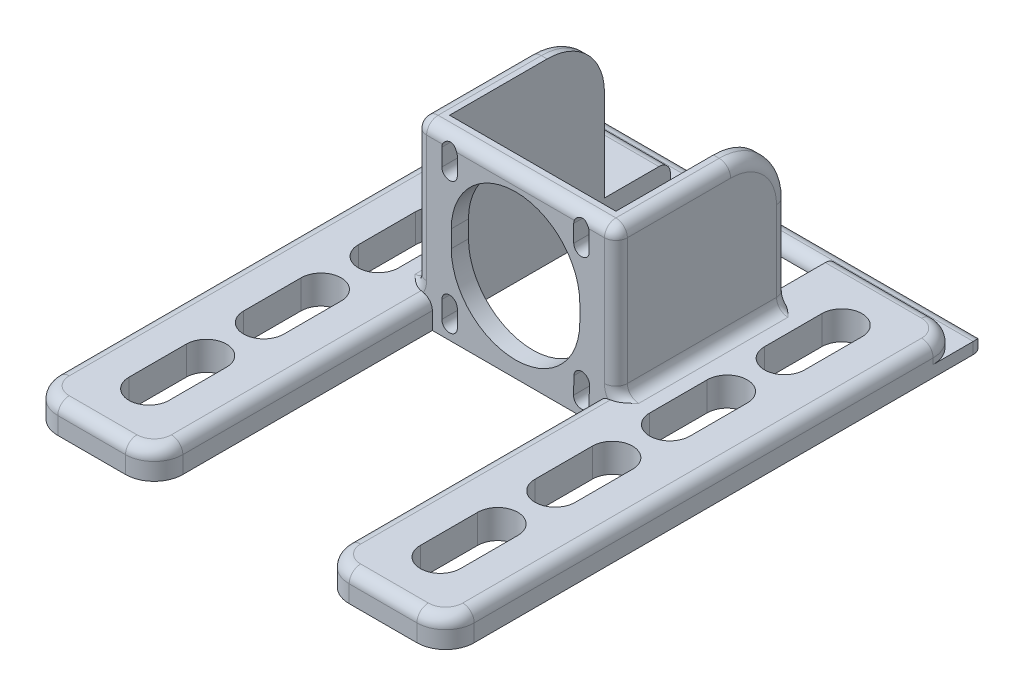
SolidWorks part; units mm, degrees
material "Grey Pro"
ref_plane "Front Plane" through (0, 0, 0) normal (0, 0, 1) x (1, 0, 0)
ref_plane "Top Plane" through (0, 0, 0) normal (0, 1, 0) x (1, 0, 0)
ref_plane "Right Plane" through (0, 0, 0) normal (1, 0, 0) x (0, 0, -1)
sketch "Sketch6" plane through (0, 0, 0) normal (0, 0, 1) x (1, 0, 0)
  line L0 (14.5, -14.5) -> (-14.5, -14.5) construction
  line L1 (14.5, 14.5) -> (14.5, -14.5)
  line L2 (-14.5, 14.5) -> (14.5, 14.5) construction
  line L3 (-14.5, -14.5) -> (-14.5, 14.5)
  line L4 (-14.15, 14.5) -> (-14.15, -14.5) construction
  line L5 (14.15, 14.5) -> (14.15, -14.5)
  line L6 (-14.15, 0) -> (14.15, 0) construction
  line L7 (-11.5, -10) -> (-11.5, -13) construction
  line L8 (-11.5, 11.5) -> (11.5, -11.5) construction
  line L9 (11.5, 11.5) -> (-11.5, -11.5) construction
  line L10 (-10.15, -10) -> (-10.15, -13)
  line L11 (-12.85, -10) -> (-12.85, -13)
  line L12 (11.5378, -10.0005) -> (11.4622, -12.9995) construction
  line L13 (10.1882, -9.9664) -> (10.1126, -12.9655)
  line L14 (12.8874, -10.0345) -> (12.8118, -13.0336)
  line L15 (-11.5, 10) -> (-11.5, 13) construction
  line L16 (-10.15, 10) -> (-10.15, 13)
  line L17 (-12.85, 10) -> (-12.85, 13)
  line L18 (11.5, 10) -> (11.5, 13) construction
  line L19 (10.15, 10) -> (10.15, 13)
  line L20 (12.85, 10) -> (12.85, 13)
  line L21 (0, -1.5) -> (0, 1.5) construction
  line L22 (-11.2, -1.5) -> (-11.2, 1.5)
  line L23 (11.2, -1.5) -> (11.2, 1.5)
  line L24 (14.5, -14.5) -> (14.5, -15.5)
  line L26 (-14.5, 14.5) -> (-14.5, 15.5)
  line L27 (-14.5, 15.5) -> (14.5, 15.5)
  line L28 (14.5, 14.5) -> (14.5, 15.5)
  line L29 (-14.5, -15.5) -> (14.5, -15.5)
  line L30 (-14.5, -14.5) -> (-14.5, -15.5)
  circle A0 centre (-11.5, -11.5) radius 1.25 construction
  circle A1 centre (11.5, -11.5) radius 1.25 construction
  circle A2 centre (-11.5, 11.5) radius 1.25 construction
  circle A3 centre (11.5, 11.5) radius 1.25 construction
  arc A4 (-10.15, -10) -> (-12.85, -10) centre (-11.5, -10) ccw
  arc A5 (-12.85, -13) -> (-10.15, -13) centre (-11.5, -13) ccw
  arc A6 (10.1882, -9.9664) -> (12.8874, -10.0345) centre (11.5378, -10.0005) cw
  arc A7 (12.8118, -13.0336) -> (10.1126, -12.9655) centre (11.4622, -12.9995) cw
  arc A8 (-10.15, 10) -> (-12.85, 10) centre (-11.5, 10) cw
  arc A9 (-12.85, 13) -> (-10.15, 13) centre (-11.5, 13) cw
  arc A10 (10.15, 10) -> (12.85, 10) centre (11.5, 10) ccw
  arc A11 (12.85, 13) -> (10.15, 13) centre (11.5, 13) ccw
  arc A12 (-11.2, -1.5) -> (11.2, -1.5) centre (0, -1.5) ccw
  arc A13 (11.2, 1.5) -> (-11.2, 1.5) centre (0, 1.5) ccw
  point P10 (0, 0)
  point P11 (0, 14.5)
  point P24 (-11.5, -11.5)
  point P32 (11.5, -11.5)
  point P38 (-11.5, 11.5)
  point P45 (11.5, 11.5)
  point P50 (0, 0)
  point P55 (0, 0)
  point P58 (-14.5, 15)
  point P61 (-14.5, -15)
  dimension "D2" = 2.5
  dimension "D13" = 2.5
  dimension "D1" = 28.3
  dimension "D3" = 23
  dimension "D4" = 23
  dimension "D5" = 1.5
  dimension "D6" = 22.4
  dimension "D7" = 29
  dimension "D8" = 0.35
  dimension "D9" = 3
  dimension "D10" = 1
  dimension "D11" = 3
  dimension "D12" = 2.7
  dimension "D14" = 1.5
  dimension "D15" = 1.5
  dimension "D16" = 1.5005
extrude "Boss-Extrude1" add sketch "Sketch6" along normal blind 3 contours L3 L30 L29 L24 L1 L28 L27 L26 A13 L23 A12 L22 A11 L20 A10 L19 A5 L11 A4 L10 L14 A7 L13 A6 L17 A9 L16 A8 region at (14.0755, 0, 0)
sketch "Sketch8" plane through (14.5, 0, 0) normal (1, 0, 0) x (0, 0, -1)
  line L1 (-41.5, -10.5) -> (38.5, -10.5)
  line L2 (-41.5, -10.5) -> (-41.5, -15.5)
  line L3 (-41.5, -15.5) -> (38.5, -15.5)
  line L4 (38.5, -10.5) -> (38.5, -15.5)
  line L6 (0, 15.5) -> (0, -15.5) construction
  line L7 (-3, -15.5) -> (0, -15.5) construction
  dimension "D1" = 5
  dimension "D2" = 80
  dimension "D3" = 38.5
extrude "Boss-Extrude3" add sketch "Sketch8" along normal blind 21.8
sketch "Sketch9" plane through (0, -10.5, 0) normal (0, 1, 0) x (1, 0, 0)
  line L0 (-14.5, 0) -> (14.5, 0) construction
  line L1 (36.3, 38.5) -> (14.5, 38.5) construction
  line L2 (21.9, 28.5) -> (21.9, 18.5)
  line L3 (36.3, -41.5) -> (14.5, -41.5) construction
  line L4 (28.9, 28.5) -> (28.9, 18.5)
  line L5 (28.9, -11.5) -> (28.9, -21.5)
  line L6 (28.9, -21.5) -> (28.9, -31.5) construction
  line L7 (21.9, -11.5) -> (21.9, -21.5)
  line L8 (21.9, -21.5) -> (21.9, -31.5) construction
  line L9 (28.9, -1.5) -> (28.9, -11.5) construction
  line L10 (21.9, -1.5) -> (21.9, -11.5) construction
  line L11 (21.9, 18.5) -> (21.9, 8.5) construction
  line L12 (21.9, 8.5) -> (21.9, -1.5)
  line L13 (28.9, 18.5) -> (28.9, 8.5) construction
  line L14 (28.9, 8.5) -> (28.9, -1.5)
  arc A0 (28.9, 28.5) -> (21.9, 28.5) centre (25.4, 28.5) ccw
  arc A1 (21.9, 18.5) -> (28.9, 18.5) centre (25.4, 18.5) ccw
  arc A2 (28.9, 8.5) -> (21.9, 8.5) centre (25.4, 8.5) ccw
  arc A3 (21.9, -1.5) -> (28.9, -1.5) centre (25.4, -1.5) ccw
  arc A4 (28.9, -11.5) -> (21.9, -11.5) centre (25.4, -11.5) ccw
  arc A5 (28.9, -21.5) -> (21.9, -21.5) centre (25.4, -21.5) ccw construction
  arc A6 (21.9, -31.5) -> (28.9, -31.5) centre (25.4, -31.5) ccw construction
  arc A7 (21.9, -21.5) -> (28.9, -21.5) centre (25.4, -21.5) ccw
  arc A8 (28.9, -31.5) -> (21.9, -31.5) centre (25.4, -31.5) ccw construction
  arc A9 (21.9, 8.5) -> (28.9, 8.5) centre (25.4, 8.5) ccw construction
  arc A10 (28.9, -1.5) -> (21.9, -1.5) centre (25.4, -1.5) ccw construction
  arc A11 (21.9, 28.5) -> (28.9, 28.5) centre (25.4, 28.5) ccw construction
  arc A12 (28.9, 18.5) -> (21.9, 18.5) centre (25.4, 18.5) ccw construction
  arc A13 (21.9, -11.5) -> (28.9, -11.5) centre (25.4, -11.5) ccw construction
  point P4 (0, 0)
  dimension "D1" = 7
  dimension "D2" = 25.4
  dimension "D3" = 10
  dimension "D5" = 10
  dimension "D4" = 7
extrude "Cut-Extrude1" cut sketch "Sketch9" against normal up to surface (5 mm away) up to face at (12.7, -15.5, 1.5)
sketch "Sketch13" plane through (0, 0, 41.5) normal (0, 0, 1) x (1, 0, 0)
  line L5 (36.3, -15.5) -> (14.5, -15.5)
  line L6 (36.3, -15.5) -> (36.3, -10.5)
  line L7 (36.3, -10.5) -> (14.5, -10.5)
  line L8 (14.5, -15.5) -> (14.5, -10.5)
extrude "Boss-Extrude6" add sketch "Sketch13" along normal blind 10
sketch "Sketch14" plane through (0, -10.5, 0) normal (0, 1, 0) x (1, 0, 0)
  line L0 (21.9, -31.5) -> (21.9, -41.5)
  line L1 (28.9, -31.5) -> (28.9, -41.5)
  line L2 (36.3, 38.5) -> (36.3, -51.5) construction
  line L3 (28.9, -21.5) -> (28.9, -11.5) construction
  arc A0 (28.9, -31.5) -> (21.9, -31.5) centre (25.4, -31.5) ccw
  arc A1 (21.9, -41.5) -> (28.9, -41.5) centre (25.4, -41.5) ccw
  arc A3 (21.9, -21.5) -> (28.9, -21.5) centre (25.4, -21.5) ccw construction
  arc A4 (28.9, -11.5) -> (21.9, -11.5) centre (25.4, -11.5) ccw construction
  arc A5 (21.9, -1.5) -> (28.9, -1.5) centre (25.4, -1.5) ccw construction
  arc A6 (28.9, 8.5) -> (21.9, 8.5) centre (25.4, 8.5) ccw construction
  arc A7 (21.9, -31.5) -> (28.9, -31.5) centre (25.4, -31.5) ccw construction
  arc A8 (28.9, -41.5) -> (21.9, -41.5) centre (25.4, -41.5) ccw construction
  point P13 (25.4, -40.7156)
  dimension "D1" = 10
  dimension "D2" = 10
  dimension "D3" = 10
  dimension "D4" = 10
extrude "Cut-Extrude2" cut sketch "Sketch14" against normal up to surface (5 mm away) up to face at (25.4, -15.5, -23.5)
mirror "Mirror1" about plane through (0, 0, 0) normal (1, 0, 0) of "Cut-Extrude2", "Cut-Extrude1", "Boss-Extrude3", "Boss-Extrude6"
sketch "Sketch12" plane through (0, 0, 3) normal (0, 0, 1) x (1, 0, 0)
  line L0 (0, -15.5) -> (0, 15.5) construction
  line L1 (14.5, 15.5) -> (17.5, 15.5)
  line L2 (14.5, 15.5) -> (14.5, -10.5)
  line L3 (14.5, -10.5) -> (17.5, -10.5)
  line L4 (17.5, 15.5) -> (17.5, -10.5)
  line L5 (-14.5, -15.5) -> (14.5, -15.5) construction
  line L6 (-14.5, 15.5) -> (14.5, 15.5) construction
  line L7 (-14.5, -10.5) -> (-17.5, -10.5)
  line L8 (-17.5, 15.5) -> (-17.5, -10.5)
  line L9 (-14.5, 15.5) -> (-17.5, 15.5)
  line L10 (-14.5, 15.5) -> (-14.5, -10.5)
  dimension "D1" = 3
extrude "Boss-Extrude5" add sketch "Sketch12" against normal blind 30
fillet "Fillet6" radius 5 6 edges at (-36.3, -13, -38.5) (36.3, -13, -38.5) (-36.3, -13, 51.5) (-14.5, -13, 51.5) (14.5, -13, 51.5) (36.3, -13, 51.5)
fillet "Fillet7" radius 2 2 edges at (-17.5, -10.5, -12) (17.5, -10.5, -12)
fillet "Fillet9" radius 10 2 edges at (-16, 15.5, -27) (16, 15.5, -27)
fillet "Fillet10" radius 2 13 edges at (-18.0858, -9.9142, 3) (18.0858, -9.9142, 3) (-18.0858, -9.9142, -27) (-17.5, -1.5, -27) (-17.5, 12.5711, -24.0711) (18.0858, -9.9142, -27) (17.5, -1.5, -27) (17.5, 12.5711, -24.0711) (-17.5, 3.5, 3) (0, 15.5, 3) (17.5, 3.5, 3) (-17.5, 15.5, -7) (17.5, 15.5, -7)
fillet "Fillet11" radius 2 14 edges at (-22.9, -10.5, -38.5) (-34.8355, -10.5, -37.0355) (-36.3, -10.5, 6.5) (-34.8355, -10.5, 50.0355) (-25.4, -10.5, 51.5) (-15.9645, -10.5, 50.0355) (22.9, -10.5, -38.5) (34.8355, -10.5, -37.0355) (14.5, -10.5, 24.75) (15.9645, -10.5, 50.0355) (25.4, -10.5, 51.5) (34.8355, -10.5, 50.0355) (-14.5, -10.5, 24.75) (36.3, -10.5, 6.5)
sketch "Sketch17" plane through (0, -15.5, 0) normal (0, -1, 0) x (1, 0, 0)
  line L2 (-36.3, -33.5) -> (-36.3, -42.5)
  line L3 (-36.3, -42.5) -> (36.3, -42.5)
  line L4 (36.3, -42.5) -> (36.3, -33.5)
  line L5 (-31.3, -38.5) -> (31.3, -38.5)
  arc A4 (31.3, -38.5) -> (36.3, -33.5) centre (31.3, -33.5) ccw construction
  arc A5 (-36.3, -33.5) -> (-31.3, -38.5) centre (-31.3, -33.5) ccw construction
  arc A6 (31.3, -38.5) -> (36.3, -33.5) centre (31.3, -33.5) ccw
  arc A7 (-36.3, -33.5) -> (-31.3, -38.5) centre (-31.3, -33.5) ccw
  dimension "D1" = 4
extrude "Boss-Extrude10" add sketch "Sketch17" against normal blind 2
fillet "Fillet13" radius 2 4 edges at (0, -13.5, -38.5) (-36.3, -14.5, -42.5) (36.3, -14.5, -42.5) (0, -13.5, -42.5)
